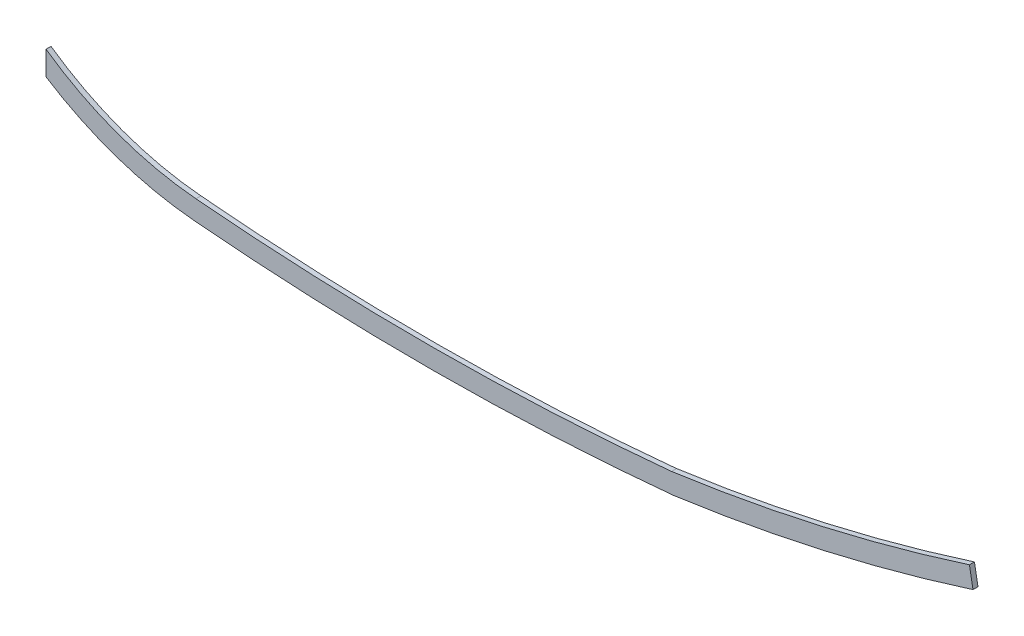
SolidWorks part; units mm, degrees
material "Balsa"
ref_plane "Front Plane" through (0, 0, 0) normal (0, 0, 1) x (1, 0, 0)
ref_plane "Top Plane" through (0, 0, 0) normal (0, 1, 0) x (1, 0, 0)
ref_plane "Right Plane" through (0, 0, 0) normal (1, 0, 0) x (0, 0, -1)
sketch "Sketch2" plane through (0, 0, 0) normal (0, 0, 1) x (1, 0, 0)
  line L0 (0, -93.726) -> (0, -78.486)
  line L2 (93.98, 0) -> (93.98, -379.755) construction
  line L3 (398.3737, -110.9898) -> (402.5381, -142.3403) construction
  line L4 (398.3737, -110.9898) -> (366.1948, 131.2634) construction
  line L5 (95.5675, -126.4975) -> (95.5675, 137.6625) construction
  line L7 (590.8643, -81.3536) -> (588.579, -68.7797)
  line L8 (0, 0) -> (672.417, 0) construction
  arc A0 (0, -93.726) -> (93.98, -125.8052) centre (112.6352, 82.55) ccw
  arc A1 (93.98, -125.8052) -> (400.2036, -124.7658) centre (241.5116, 1518.5899) ccw
  arc A2 (400.2036, -124.7658) -> (590.8643, -81.3536) centre (242.7057, 1007.3312) ccw
  arc A3 (95.6211, -113.2301) -> (398.7207, -112.1786) centre (241.5116, 1518.5899) ccw construction
  arc A4 (95.5675, -113.2253) -> (398.7207, -112.1786) centre (241.5116, 1518.5899) ccw
  arc A5 (398.7207, -112.1786) -> (588.579, -68.7797) centre (242.7057, 1007.3312) ccw
  arc A6 (94.4927, -125.8512) -> (400.2036, -124.7658) centre (241.5116, 1518.5899) ccw construction
  arc A7 (398.7207, -112.1786) -> (587.0046, -69.2844) centre (242.7057, 1007.3312) ccw construction
  arc A8 (0, -78.486) -> (95.5675, -113.2253) centre (112.6352, 82.55) ccw
  spline S0 degree 3 poles (3.7499, -94.8626) (10.597, -99.2271) (17.6385, -103.1401) (32.0968, -110.0953) (39.5136, -113.1375) (50.922, -117.0433) (54.7721, -118.2354) (60.6197, -119.8556) (62.5829, -120.3681) (66.5243, -121.3341) (68.5001, -121.787) (78.4043, -123.9021) (86.408, -125.1172) (94.4926, -125.8525) knots 0 0 0 0 0.25 0.25 0.5 0.5 0.625 0.625 0.6875 0.6875 0.75 0.75 1 1 1 1 construction
  spline S1 degree 3 poles (94.4926, -125.8525) (120.9278, -128.4258) (173.8258, -132.179) (226.7788, -133.168) (266.5142, -132.8729) (279.7628, -132.6016) (299.6408, -131.9345) (306.2677, -131.6688) (319.5231, -131.0505) (326.1536, -130.6977) (359.2877, -128.7173) (385.6949, -126.4433) (412.003, -123.4859) knots 0 0 0 0 0.25 0.5 0.5 0.625 0.625 0.6875 0.6875 0.75 0.75 1 1 1 1 construction
  dimension "D3" = 82.55
  dimension "D4" = 1651
  dimension "D5" = 1143
  dimension "D6" = 79.699
  dimension "D1" = 15.24
  dimension "D2" = 93.726
extrude "Boss-Extrude1" add sketch "Sketch2" along normal blind 3.175
